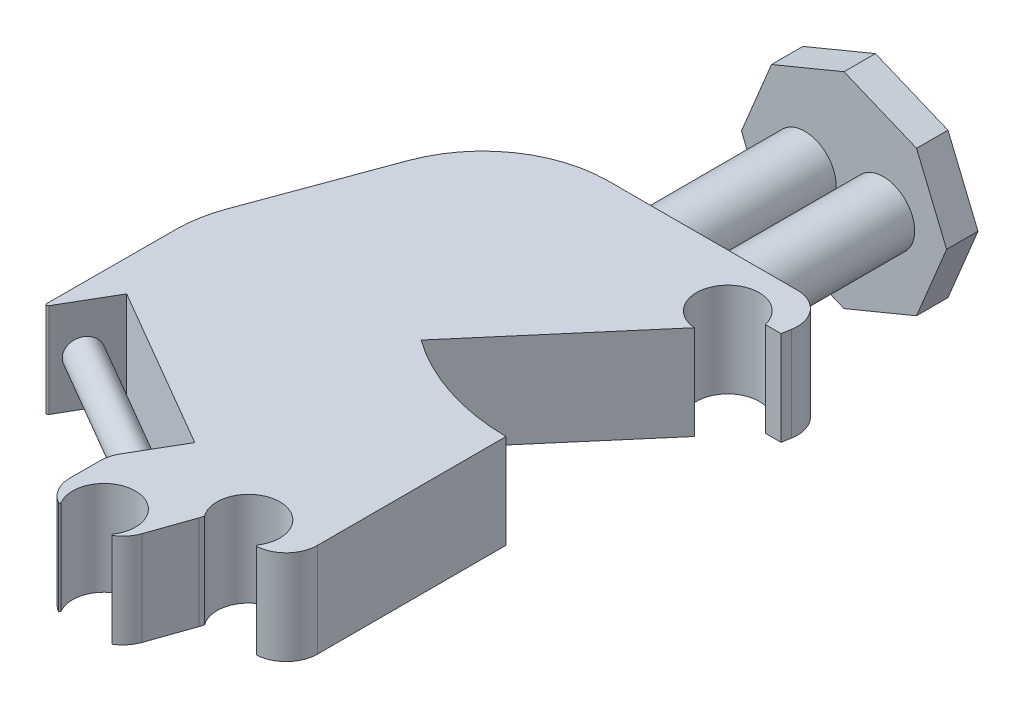
SolidWorks part; units mm, degrees
ref_plane "Front Plane" through (0, 0, 0) normal (0, 0, 1) x (1, 0, 0)
ref_plane "Top Plane" through (0, 0, 0) normal (0, 1, 0) x (1, 0, 0)
ref_plane "Right Plane" through (0, 0, 0) normal (1, 0, 0) x (0, 0, -1)
ref_plane "Plane1" through (0, -7.5, 0) normal (0, 1, 0) x (1, 0, 0)
sketch "Sketch1" plane through (0, -7.5, 0) normal (0, 1, 0) x (1, 0, 0)
  line L0 (-3.3112, 103.3764) -> (-8.3112, 103.3764)
  line L1 (-8.3112, 103.3764) -> (-8.3112, 78.3764)
  line L2 (-8.3112, 78.3764) -> (-3.3112, 78.3764)
  line L3 (-3.3112, 78.3764) -> (-3.3112, 103.3764)
  line L4 (-8.3112, 103.3764) -> (-8.3112, 78.3764) construction
revolve "Revolve1" add sketch "Sketch1" angle 360 about L4 reverse direction yes
ref_plane "Plane2" through (0, -2.5, 0) normal (0, 1, 0) x (1, 0, 0)
sketch "Sketch2" plane through (0, -2.5, 0) normal (0, 1, 0) x (1, 0, 0)
  line L0 (-20.9042, -4.0606) -> (-17.7458, -10)
  line L1 (-15.5719, -7.3481) -> (-13.2352, -0.6719)
  line L2 (0, 5) -> (0, 35)
  line L3 (-20.058, 41.5415) -> (5.1978, 71.09)
  line L4 (5.1978, 71.09) -> (8.9826, 71.09)
  line L5 (8.9826, 71.09) -> (8.9826, 78.3764)
  line L6 (8.9826, 78.3764) -> (-8.3112, 78.3764)
  line L7 (-8.3112, 78.3764) -> (-41.0174, 78.3764)
  line L8 (-41.0174, 78.3764) -> (-54.8193, 40.833)
  line L9 (-54.8193, 40.833) -> (-54.897, 16.7662)
  line L10 (-54.4309, 16.6397) -> (-49.8721, 24.4773)
  line L11 (-49.8721, 24.4773) -> (-8.9678, 0.6849)
  line L12 (-8.9678, 0.6849) -> (-28.9677, 0.7494)
  line L13 (-28.9677, 0.7494) -> (-28.9876, -5.4067)
  line L14 (-26.4535, -9.7725) -> (-20.9042, -4.0606)
  arc A0 (-17.7458, -10) -> (-15.5719, -7.3481) centre (-20.2911, -5.6964) ccw
  arc A1 (-13.2352, -0.6719) -> (-13.0407, 0.0551) centre (-17.9545, 0.9798) ccw
  arc A2 (-13.0407, 0.0551) -> (-5, 0) centre (-9, 3) ccw
  arc A3 (-5, 0) -> (0, 5) centre (-5, 5) ccw
  arc A4 (0, 35) -> (-20.058, 41.5415) centre (0.3184, 69.9986) cw
  arc A5 (-54.897, 16.7662) -> (-54.4309, 16.6397) centre (-54.647, 16.7654) ccw
  arc A6 (-28.9876, -5.4067) -> (-26.4535, -9.7725) centre (-23.9876, -5.4228) ccw
extrude "Boss-Extrude1" add sketch "Sketch2" against normal blind 10
sketch "Sketch3" plane through (0, -12.5, 0) normal (0, -1, 0) x (1, 0, 0)
  line L0 (-20.9042, 4.0606) -> (-17.7458, 10)
  line L1 (-15.5719, 7.3481) -> (-13.2352, 0.6719)
  line L2 (0, -5) -> (0, -35)
  line L3 (-20.058, -41.5415) -> (5.1978, -71.09)
  line L4 (5.1978, -71.09) -> (8.9826, -71.09)
  line L5 (8.9826, -71.09) -> (8.9826, -78.3764)
  line L6 (8.9826, -78.3764) -> (-41.0174, -78.3764)
  line L7 (-41.0174, -78.3764) -> (-54.8193, -40.833)
  line L8 (-54.8193, -40.833) -> (-54.897, -16.7662)
  line L9 (-54.4309, -16.6397) -> (-49.8721, -24.4773)
  line L10 (-49.8721, -24.4773) -> (-8.9678, -0.6849)
  line L11 (-8.9678, -0.6849) -> (-28.9677, -0.7494)
  line L12 (-28.9677, -0.7494) -> (-28.9876, 5.4067)
  line L13 (-26.4535, 9.7725) -> (-20.9042, 4.0606)
  arc A0 (-17.7458, 10) -> (-15.5719, 7.3481) centre (-20.2911, 5.6964) cw
  arc A1 (-13.2352, 0.6719) -> (-13.0407, -0.0551) centre (-17.9545, -0.9798) cw
  arc A2 (-13.0407, -0.0551) -> (-5, 0) centre (-9, -3) cw
  arc A3 (-5, 0) -> (0, -5) centre (-5, -5) cw
  arc A4 (0, -35) -> (-20.058, -41.5415) centre (0.3184, -69.9986) ccw
  arc A5 (-54.897, -16.7662) -> (-54.4309, -16.6397) centre (-54.647, -16.7654) cw
  arc A6 (-28.9876, 5.4067) -> (-26.4535, 9.7725) centre (-23.9876, 5.4228) cw
extrude "Boss-Extrude2" add sketch "Sketch3" along normal blind 2.5
sketch "Sketch4" plane through (0, -2.5, 0) normal (0, 1, 0) x (-1, 0, 0)
  line L0 (20.9042, 4.0606) -> (26.4535, 9.7725)
  line L1 (28.9876, 5.4067) -> (28.9677, -0.7494)
  line L2 (28.9677, -0.7494) -> (8.9678, -0.6849)
  line L3 (8.9678, -0.6849) -> (49.8721, -24.4773)
  line L4 (49.8721, -24.4773) -> (54.4309, -16.6397)
  line L5 (54.897, -16.7662) -> (54.8193, -40.833)
  line L6 (54.8193, -40.833) -> (41.0174, -78.3764)
  line L7 (41.0174, -78.3764) -> (-8.9826, -78.3764)
  line L8 (-8.9826, -78.3764) -> (-8.9826, -71.09)
  line L9 (-8.9826, -71.09) -> (-5.1978, -71.09)
  line L10 (-5.1978, -71.09) -> (20.058, -41.5415)
  line L11 (0, -35) -> (0, -5)
  line L12 (13.2352, 0.6719) -> (15.5719, 7.3481)
  line L13 (17.7458, 10) -> (20.9042, 4.0606)
  arc A0 (26.4535, 9.7725) -> (28.9876, 5.4067) centre (23.9876, 5.4228) cw
  arc A1 (54.4309, -16.6397) -> (54.897, -16.7662) centre (54.647, -16.7654) cw
  arc A2 (20.058, -41.5415) -> (0, -35) centre (-0.3184, -69.9986) ccw
  arc A3 (0, -5) -> (5, 0) centre (5, -5) cw
  arc A4 (5, 0) -> (13.0407, -0.0551) centre (9, -3) cw
  arc A5 (13.0407, -0.0551) -> (13.2352, 0.6719) centre (17.9545, -0.9798) cw
  arc A6 (15.5719, 7.3481) -> (17.7458, 10) centre (20.2911, 5.6964) cw
extrude "Boss-Extrude3" add sketch "Sketch4" along normal blind 2.5
ref_plane "Plane3" through (0, 0, -103.3764) normal (0, 0, 1) x (1, 0, 0)
sketch "Sketch5" plane through (0, 0, -103.3764) normal (0, 0, 1) x (1, 0, 0)
  line L0 (-3.0127, 4.0485) -> (-14.5612, 8.832)
  line L1 (-14.5612, 8.832) -> (-26.1097, 4.0485)
  line L2 (-26.1097, 4.0485) -> (-30.8933, -7.5)
  line L3 (-30.8933, -7.5) -> (-26.1097, -19.0485)
  line L4 (-26.1097, -19.0485) -> (-14.5612, -23.832)
  line L5 (-14.5612, -23.832) -> (-3.0127, -19.0485)
  line L6 (-3.0127, -19.0485) -> (1.7708, -7.5)
  line L7 (1.7708, -7.5) -> (-3.0127, 4.0485)
extrude "Boss-Extrude4" add sketch "Sketch5" against normal blind 5
draft "Draft1" type of draft neutral plane draft angle 60 faces to draft 1 face at (-18.9678, -7.5, -0.7172) neutral plane through (-28.9677, -12.5, -0.7494) neutral plane normal (-1, 0, -0.0032) parameters "D1"=60
draft "Draft2" type of draft neutral plane draft angle 10 faces to draft 1 face at (8.9826, -7.5, -74.7332) neutral plane through (-8.3112, -12.5, -78.3764) neutral plane normal (0, 0, -1) reverse direction yes parameters "D1"=10
ref_plane "Plane4" through (0, 0, 7) normal (0, 0, 1) x (1, 0, 0)
sketch "Sketch6" plane through (0, 0, 7) normal (0, 0, 1) x (1, 0, 0)
  line L0 (-17, 0) -> (-22, 0)
  line L1 (-22, 0) -> (-22, -15)
  line L2 (-22, -15) -> (-17, -15)
  line L3 (-17, -15) -> (-17, 0)
  line L4 (-22, 0) -> (-22, -15) construction
revolve "Cut-Revolve1" cut sketch "Sketch6" angle 360 about L4 reverse direction yes
ref_plane "Plane5" through (0, 0, -3) normal (0, 0, -1) x (-1, 0, 0)
sketch "Sketch7" plane through (0, 0, -3) normal (0, 0, -1) x (-1, 0, 0)
  line L0 (4, -15) -> (9, -15)
  line L1 (9, -15) -> (9, 0)
  line L2 (9, 0) -> (4, 0)
  line L3 (4, 0) -> (4, -15)
  line L4 (9, -15) -> (9, 0) construction
revolve "Cut-Revolve2" cut sketch "Sketch7" angle 360 about L4 reverse direction yes
sketch "Sketch8" plane through (0, -7.5, 0) normal (0, 1, 0) x (1, 0, 0)
  line L0 (-15.8112, 103.3764) -> (-20.8112, 103.3764)
  line L1 (-20.8112, 103.3764) -> (-20.8112, 78.3764)
  line L2 (-20.8112, 78.3764) -> (-15.8112, 78.3764)
  line L3 (-15.8112, 78.3764) -> (-15.8112, 103.3764)
  line L4 (-20.8112, 103.3764) -> (-20.8112, 78.3764) construction
revolve "Revolve2" add sketch "Sketch8" angle 360 about L4 reverse direction yes
sketch "Sketch9" plane through (0, -7.5, 0) normal (0, 1, 0) x (1, 0, 0)
  line L0 (-51.1291, 22.3162) -> (-52.386, 20.1552)
  line L1 (-52.386, 20.1552) -> (-26.4538, 5.0715)
  line L2 (-26.4538, 5.0715) -> (-25.1968, 7.2325)
  line L3 (-25.1968, 7.2325) -> (-51.1291, 22.3162)
  line L4 (-53.3252, 20.7015) -> (-25.5146, 4.5252) construction
revolve "Revolve3" add sketch "Sketch9" angle 360 about L4 reverse direction yes
hole_wizard "Ø10.0 (10) Diameter Hole1" positions "Sketch11" profile "Sketch10" hole size "Ø10.0" standard "ANSI Metric"
sketch "Sketch11" plane through (0, -15, 0) normal (0, -1, 0) x (-1, 0, 0)
  point P0 (-0.3184, 69.9986)
sketch "Sketch10" plane through (0.3184, -15, -69.9986) normal (1, 0, 0) x (0, 0, -1)
  line L0 (0, 0) -> (0, 23.832)
  line L1 (0, 23.832) -> (5, 23.832)
  line L2 (5, 23.832) -> (5, 0)
  line L5 (5, 0) -> (0, 0)
  line L11 (0, -6.35) -> (0, 107.95) construction
  dimension "Thru Hole Dia." = 10
  dimension "Thru Hole Depth" = 23.832
chamfer "Chamfer1" distance 0.2628 angle 63.474 1 edges at (-5, -7.5, 0) first distance on face at (-1.9822, -7.5, -1.9822)
fillet "Fillet1" radius 5 2 edges at (8.9826, -7.5, -78.3764) (-28.9677, -7.5, -0.7494) tangent propagation no
fillet "Fillet2" radius 20 2 edges at (-41.0174, -7.5, -78.3764) (-54.8193, -7.5, -40.833) tangent propagation no
